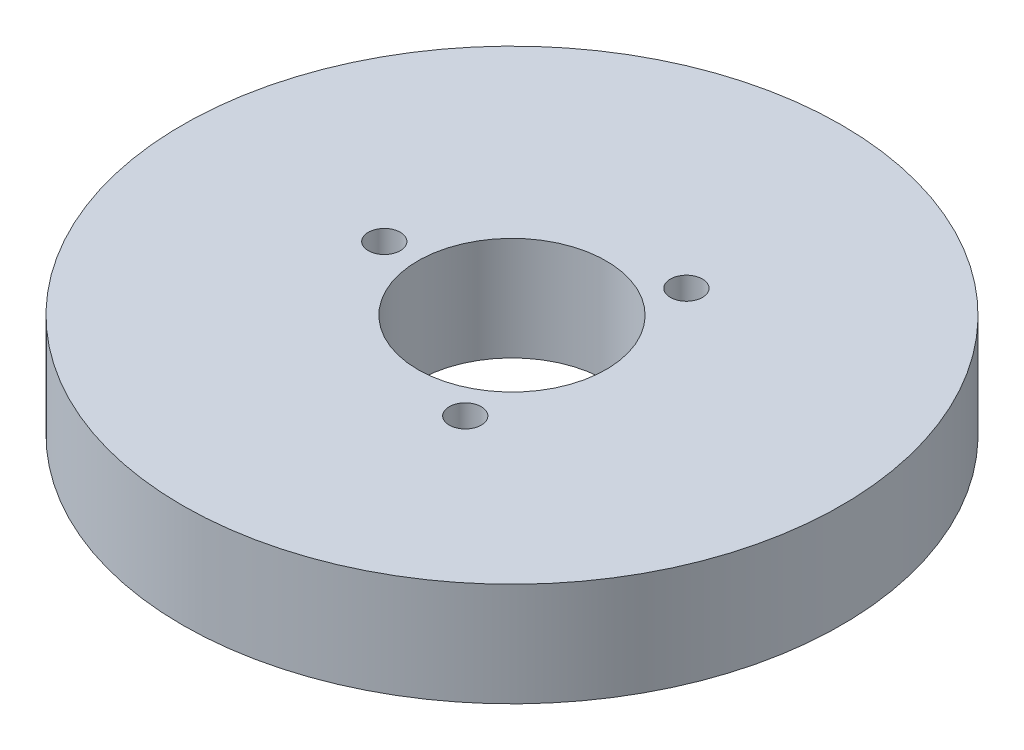
SolidWorks part; units mm, degrees
ref_plane "Front Plane" through (0, 0, 0) normal (0, 0, 1) x (1, 0, 0)
ref_plane "Top Plane" through (0, 0, 0) normal (0, 1, 0) x (1, 0, 0)
ref_plane "Right Plane" through (0, 0, 0) normal (1, 0, 0) x (0, 0, -1)
sketch "Sketch1" plane through (0, 0, 0) normal (0, 1, 0) x (1, 0, 0)
  circle A0 centre (0, 0) radius 70
  dimension "FLANGE_OD" = 140
extrude "Boss-Extrude1" add sketch "Sketch1" along normal blind 22
sketch "Sketch2" plane through (0, 0, 0) normal (0, 1, 0) x (1, 0, 0)
  circle A0 centre (0, 0) radius 20
  dimension "BORE_D" = 40
extrude "Cut-Extrude1" cut sketch "Sketch2" along normal through all
sketch "Sketch3" plane through (0, 22, 0) normal (0, 1, 0) x (1, 0, 0)
  circle A0 centre (0, 0) radius 27.1213 construction
  circle A1 centre (-27.1213, 0) radius 3.4
  dimension "BOLT_D" = 6.8
  dimension "BOLT_PCD" = 54.2426
extrude "Cut-Extrude2" cut sketch "Sketch3" against normal blind 17.603
pattern_circular "CirPattern1" count 3 over 360 about axis through (0, 0, 0) along (0, 1, 0) of "Cut-Extrude2"
